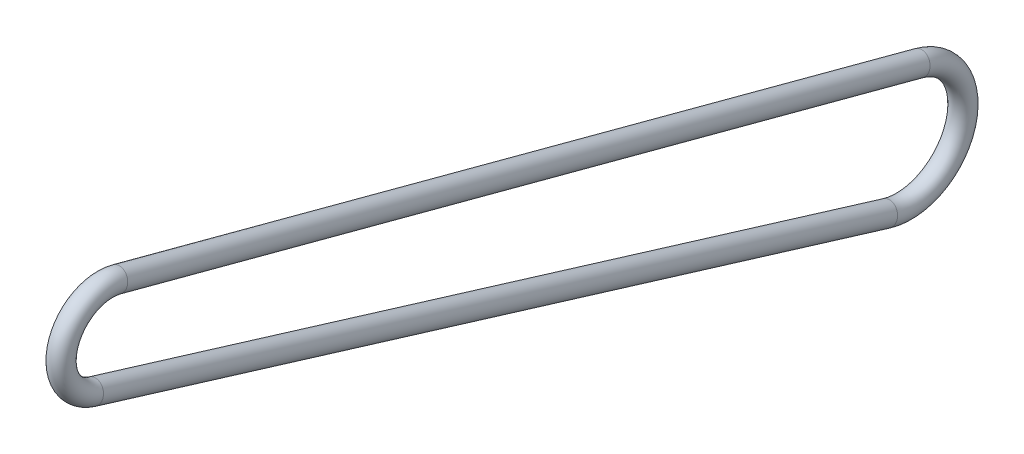
SolidWorks part; units mm, degrees
ref_plane "Front" through (0, 0, 0) normal (0, 0, 1) x (1, 0, 0)
ref_plane "Top" through (0, 0, 0) normal (0, 1, 0) x (1, 0, 0)
ref_plane "Right" through (0, 0, 0) normal (1, 0, 0) x (0, 0, -1)
ref_axis "side-side" through (80.9, 0, 0) along (-1, 0, 0)
ref_axis "up-down" through (0, 50, 0) along (0, -1, 0)
ref_axis "front-back" through (0, 0, -80.9) along (0, 0, 1)
sketch "Sketch1" plane through (0, 0, 0) normal (1, 0, 0) x (0, 0, -1)
  line L0 (2.118, 7.9425) -> (151.1987, -31.8118)
  line L1 (-2.4027, -7.8611) -> (145.1492, -52.96)
  arc A0 (2.118, 7.9425) -> (-2.4027, -7.8611) centre (0, 0) ccw
  arc A1 (145.1492, -52.96) -> (151.1987, -31.8118) centre (148.3645, -42.4404) ccw
  circle A2 centre (148.3645, -42.4404) radius 11 construction
  dimension "D1" = 22
  dimension "D2" = 154.2903
ref_plane "Plane1" through (0, 7.9425, -2.118) normal (0, -0.2577, -0.9662) x (-1, 0, 0)
sketch "Sketch2" plane through (0, 7.9425, -2.118) normal (0, -0.2577, -0.9662) x (-1, 0, 0)
  circle A0 centre (0, 0) radius 1.9844
  dimension "D1" = 3.9688
sweep "Sweep1" add profiles "Sketch2" path "Sketch1"
sketch "Sketch3" plane through (0, 0, 0) normal (1, 0, 0) x (0, 0, -1)
  line L0 (145.7292, -51.0623) -> (-1.8227, -5.9634)
  line L1 (-2.9828, -9.7588) -> (144.5692, -54.8577)
  line L2 (-2.9828, -9.7588) -> (144.5692, -54.8577)
  line L3 (145.7292, -51.0623) -> (-1.8227, -5.9634)
  line L4 (1.6067, 6.0252) -> (150.6875, -33.7292)
  line L5 (151.71, -29.8945) -> (2.6293, 9.8599)
  line L6 (151.71, -29.8945) -> (2.6293, 9.8599)
  line L7 (1.6067, 6.0252) -> (150.6875, -33.7292)
  arc A0 (145.7292, -51.0623) -> (150.6875, -33.7292) centre (148.3645, -42.4404) ccw
  arc A1 (144.5692, -54.8577) -> (151.71, -29.8945) centre (148.3645, -42.4404) ccw
  arc A2 (144.5692, -54.8577) -> (151.71, -29.8945) centre (148.3645, -42.4404) ccw
  arc A3 (145.7292, -51.0623) -> (150.6875, -33.7292) centre (148.3645, -42.4404) ccw
  arc A4 (1.6067, 6.0252) -> (-1.8227, -5.9634) centre (0, 0) ccw
  arc A5 (2.6293, 9.8599) -> (-2.9828, -9.7588) centre (0, 0) ccw
  arc A6 (2.6293, 9.8599) -> (-2.9828, -9.7588) centre (0, 0) ccw
  arc A7 (1.6067, 6.0252) -> (-1.8227, -5.9634) centre (0, 0) ccw
